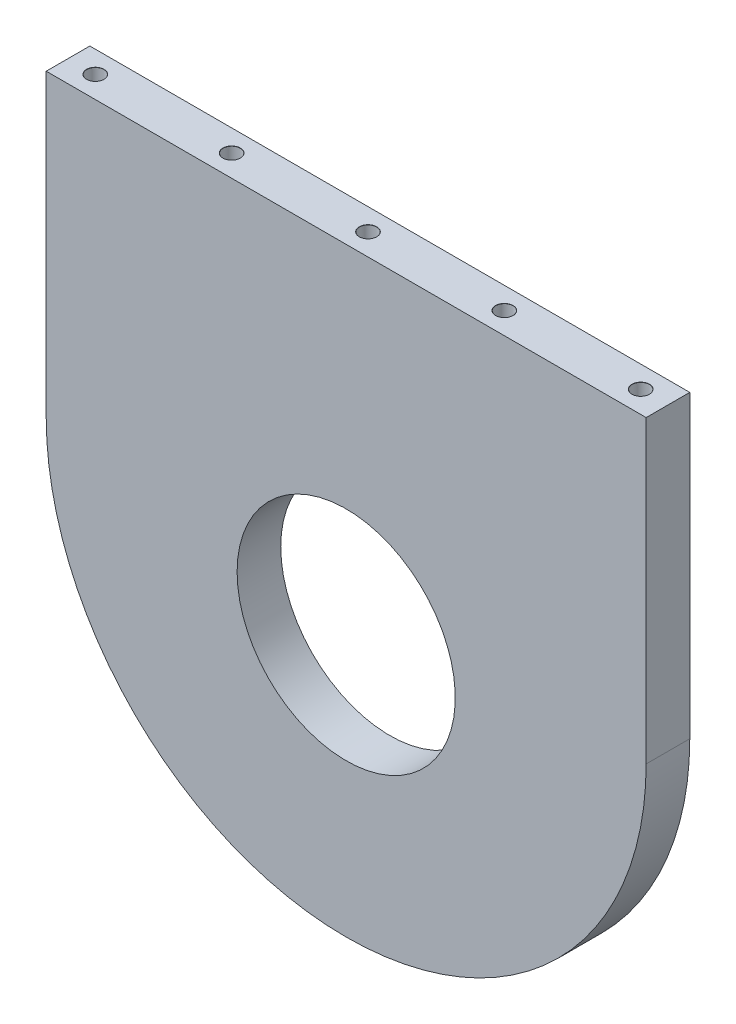
SolidWorks part; units mm, degrees
material "6061-T6 (SS)"
ref_plane "Front Plane" through (0, 0, 0) normal (0, 0, 1) x (1, 0, 0)
ref_plane "Top Plane" through (0, 0, 0) normal (0, 1, 0) x (1, 0, 0)
ref_plane "Right Plane" through (0, 0, 0) normal (1, 0, 0) x (0, 0, -1)
sketch "Sketch1" plane through (0, 0, 0) normal (0, 0, 1) x (1, 0, 0)
  line L1 (0, 0) -> (110, 0)
  line L2 (0, 0) -> (0, 110)
  line L3 (0, 110) -> (110, 110)
  line L4 (110, 0) -> (110, 110)
  dimension "D1" = 110
  dimension "D2" = 110
extrude "Boss-Extrude1" add sketch "Sketch1" along normal blind 8
sketch "Sketch2" plane through (0, 110, 0) normal (0, 1, 0) x (1, 0, 0)
  line L0 (0, -4) -> (110, -4) construction
  line L1 (0, -8) -> (0, 0) construction
  line L2 (110, -8) -> (110, 0) construction
  point P9 (55, -4)
  point P18 (80, -4)
  point P19 (105, -4)
  point P20 (55, -4)
  point P21 (80, -4)
  point P22 (30, -4)
  point P23 (55, -4)
  point P24 (30, -4)
  point P25 (5, -4)
  dimension "D1" = 3
  dimension "D2" = 3
hole_wizard "Tap Drill for M3 Helicoil1" positions "Sketch2" profile "Sketch4" hole size "M3x0.5" standard "DIN"
sketch "Sketch4" plane through (5, 110, 4) normal (1, 0, 0) x (0, 0, 1)
  line L0 (0, 0) -> (0, 6.9464)
  line L1 (0, 6.9464) -> (1.575, 6)
  line L2 (1.575, 6) -> (1.575, 0.025)
  line L3 (1.575, 0.025) -> (1.6, 0)
  line L5 (1.6, 0) -> (0, 0)
  line L6 (-1.575, 0.025) -> (-1.6, 0) construction
  line L10 (0, 6.9464) -> (-1.575, 6) construction
  line L11 (0, -6.35) -> (0, 107.95) construction
  dimension "Hole Dia." = 3.15
  dimension "Hole Depth" = 6
  dimension "Near C'Sink Dia." = 3.2
  dimension "Near C'Sink Angle" = 90
  dimension "Drill Angle" = 118
sketch "Sketch5" plane through (0, 0, 0) normal (0, 0, -1) x (-1, 0, 0)
  circle A0 centre (-55, 48) radius 40 construction
  point P8 (-55, 48)
hole_wizard "Ø40.0 (40) Diameter Hole1" positions "Sketch5" profile "Sketch7" hole size "Ø40.0" standard "DIN" end condition through all
sketch "Sketch7" plane through (55, 48, 0) normal (1, 0, 0) x (0, 1, 0)
  line L0 (0, 0) -> (0, 8)
  line L1 (0, 8) -> (20, 8)
  line L2 (20, 8) -> (20, 0)
  line L5 (20, 0) -> (0, 0)
  line L11 (0, -6.35) -> (0, 107.95) construction
  dimension "Thru Hole Dia." = 40
  dimension "Thru Hole Depth" = 8
fillet "Fillet1" radius 55 2 edges at (110, 0, 4) (0, 0, 4)
sketch "Sketch8" plane through (0, 0, 0) normal (0, 0, -1) x (-1, 0, 0)
  line L0 (-27, 89.95) -> (-27, 109.95)
  line L1 (-2, 89.95) -> (-8, 89.95)
  line L2 (-2, 89.95) -> (-2, 109.95)
  line L3 (-106.575, 109.975) -> (-103.425, 109.975) construction
  line L4 (-78.4, 110) -> (-81.6, 110) construction
  line L5 (-56.575, 109.975) -> (-53.425, 109.975) construction
  line L6 (-104, 104) -> (-104, 55)
  line L7 (-6, 55) -> (-6, 104)
  line L8 (-6, 104) -> (-104, 104)
  line L9 (-104, 104) -> (-104, 55)
  line L10 (-6, 55) -> (-6, 104)
  line L11 (-6, 104) -> (-104, 104)
  line L12 (-31.575, 109.975) -> (-28.425, 109.975) construction
  line L13 (-6.575, 109.975) -> (-3.425, 109.975) construction
  line L14 (-106.575, 109.975) -> (-103.425, 109.975)
  line L15 (-78.4, 110) -> (-81.6, 110)
  line L16 (-56.575, 109.975) -> (-53.425, 109.975)
  line L17 (-31.575, 109.975) -> (-28.425, 109.975)
  line L18 (-6.575, 109.975) -> (-3.425, 109.975)
  line L19 (-2, 109.95) -> (-8, 110)
  line L20 (-110, 110) -> (0, 110) construction
  line L21 (-27, 109.95) -> (-33, 110)
  line L22 (-52, 109.95) -> (-58, 110)
  line L23 (-76.9999, 110) -> (-83.0001, 110)
  line L24 (-101.9999, 109.975) -> (-108.0001, 109.975)
  line L25 (-2, 109.95) -> (-8, 109.95)
  line L26 (-8, 89.95) -> (-8, 109.95)
  line L27 (-27, 89.95) -> (-33, 89.95)
  line L28 (-33, 89.95) -> (-33, 109.95)
  line L29 (-27, 109.95) -> (-33, 109.95)
  line L30 (-52, 89.95) -> (-52, 109.95)
  line L31 (-52, 89.95) -> (-58, 89.95)
  line L32 (-58, 89.95) -> (-58, 109.95)
  line L33 (-52, 109.95) -> (-58, 109.95)
  line L34 (-77, 89.95) -> (-77, 109.95)
  line L35 (-77, 89.95) -> (-83, 89.95)
  line L36 (-83, 89.95) -> (-83, 109.95)
  line L37 (-77, 109.95) -> (-83, 109.95)
  line L38 (-102, 89.95) -> (-102, 109.95)
  line L39 (-102, 89.95) -> (-108, 89.95)
  line L40 (-108, 89.95) -> (-108, 109.95)
  line L41 (-102, 109.95) -> (-108, 109.95)
  line L42 (-102, 89.95) -> (-104, 87.95)
  line L43 (-8, 89.95) -> (-6, 87.95)
  circle A2 centre (-55, 48) radius 26
  circle A3 centre (-55, 48) radius 26
  arc A7 (-104, 55) -> (-55, 6) centre (-55, 55) ccw
  arc A8 (-55, 6) -> (-6, 55) centre (-55, 55) ccw
  arc A9 (-104, 55) -> (-55, 6) centre (-55, 55) ccw
  arc A10 (-55, 6) -> (-6, 55) centre (-55, 55) ccw
  point P25 (-5, 109.975)
  point P28 (-30, 109.975)
  point P31 (-55, 109.975)
  point P34 (-80, 110)
  point P37 (-105, 109.975)
  dimension "D3" = 6
  dimension "D4" = 20
  dimension "D5" = 5
  dimension "D6" = 45
  dimension "D7" = 45
  dimension "D1" = 6
  dimension "D2" = 6
extrude "Cut-Extrude1" cut sketch "Sketch8" against normal blind 5 contours A9 A10 L10 L1 L26 L11 L0 L27 L28 L30 L31 L32 L34 L35 L36 L38 L39 L9 A3 region at (25.6141, 96.975, 0)
fillet "Fillet2" radius 4 2 edges at (6, 87.95, 2.5) (104, 87.95, 2.5)
fillet "Fillet3" radius 2 2 edges at (8, 89.95, 2.5) (102, 89.95, 2.5)
fillet "Fillet5" radius 4 8 edges at (33, 104, 2.5) (58, 104, 2.5) (83, 104, 2.5) (102, 104, 2.5) (77, 104, 2.5) (52, 104, 2.5) (27, 104, 2.5) (8, 104, 2.5)
sketch "Sketch9" plane through (0, 0, 5) normal (0, 0, -1) x (-1, 0, 0)
  line L1 (-58, 22.1737) -> (-52, 22.1737)
  line L2 (-58, 22.1737) -> (-58, 6)
  line L3 (-58, 6) -> (-52, 6)
  line L4 (-52, 22.1737) -> (-52, 6)
  line L5 (-29.1737, 51) -> (-6.1635, 51)
  line L6 (-29.1737, 51) -> (-29.1737, 45)
  line L7 (-29.1737, 45) -> (-6.1635, 45)
  line L8 (-6.1635, 51) -> (-6.1635, 45)
  line L9 (-80.8263, 45) -> (-103.8365, 45)
  line L10 (-80.8263, 45) -> (-80.8263, 51)
  line L11 (-80.8263, 51) -> (-103.8365, 51)
  line L12 (-103.8365, 45) -> (-103.8365, 51)
  line L13 (-55, 48) -> (-55, 6) construction
  line L14 (-55, 48) -> (-103.8365, 48) construction
  line L15 (-55, 48) -> (-6.1635, 48) construction
  line L16 (-52, 89.95) -> (-52, 100) construction
  line L17 (-58, 89.95) -> (-52, 89.95)
  line L18 (-58, 89.95) -> (-58, 73.8263)
  line L19 (-58, 73.8263) -> (-52, 73.8263)
  line L20 (-52, 89.95) -> (-52, 73.8263)
  circle A0 centre (-55, 48) radius 26 construction
  arc A1 (-104, 55) -> (-6, 55) centre (-55, 55) ccw construction
  arc A2 (-104, 55) -> (-6, 55) centre (-55, 55) ccw construction
  point P17 (0, 0)
  point P32 (0, 0)
  dimension "D1" = 6
extrude "Boss-Extrude2" add sketch "Sketch9" along normal up to surface (5 mm away) up to face at (55, 92.205, 0)
fillet "Fillet6" radius 4 14 edges at (29.1737, 51, 2.5) (6.1635, 51, 2.5) (80.8263, 51, 2.5) (103.8365, 51, 2.5) (58, 6.0919, 2.5) (58, 22.1737, 2.5) (80.8263, 45, 2.5) (102.9687, 45, 2.5) (52, 22.1737, 2.5) (52, 6.0919, 2.5) (7.0313, 45, 2.5) (29.1737, 45, 2.5) (52, 73.8263, 2.5) (58, 73.8263, 2.5)
